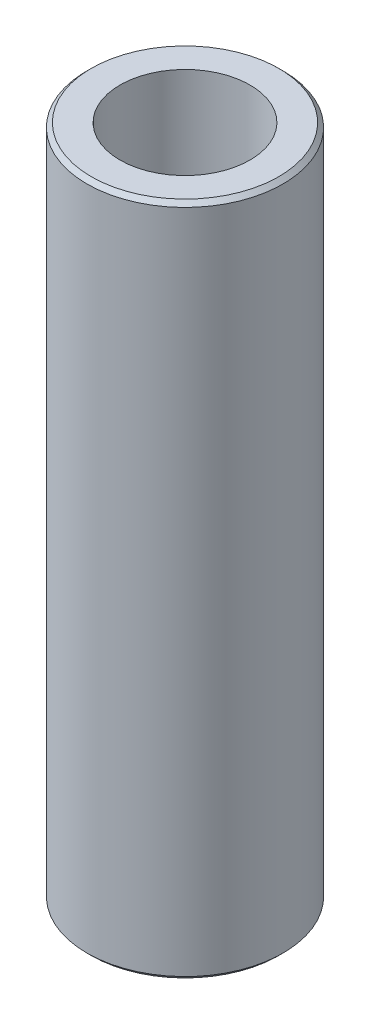
SolidWorks part; units mm, degrees
ref_plane "Front Plane" through (0, 0, 0) normal (0, 0, 1) x (1, 0, 0)
ref_plane "Top Plane" through (0, 0, 0) normal (0, 1, 0) x (1, 0, 0)
ref_plane "Right Plane" through (0, 0, 0) normal (1, 0, 0) x (0, 0, -1)
sketch "Sketch1" plane through (0, 0, 0) normal (0, 1, 0) x (1, 0, 0)
  circle A0 centre (0, 0) radius 45
  dimension "SHAFT_OD" = 90
extrude "Boss-Extrude1" add sketch "Sketch1" along normal blind 309.6463
sketch "Sketch2" plane through (0, 0, 0) normal (0, 1, 0) x (1, 0, 0)
  circle A0 centre (0, 0) radius 29.8491
  dimension "BORE_D" = 59.6982
extrude "Cut-Extrude1" cut sketch "Sketch2" along normal through all
chamfer "Chamfer1" distance 1.9406 angle 45 2 edges at (0, 309.6463, 45) (0, 0, 45)
